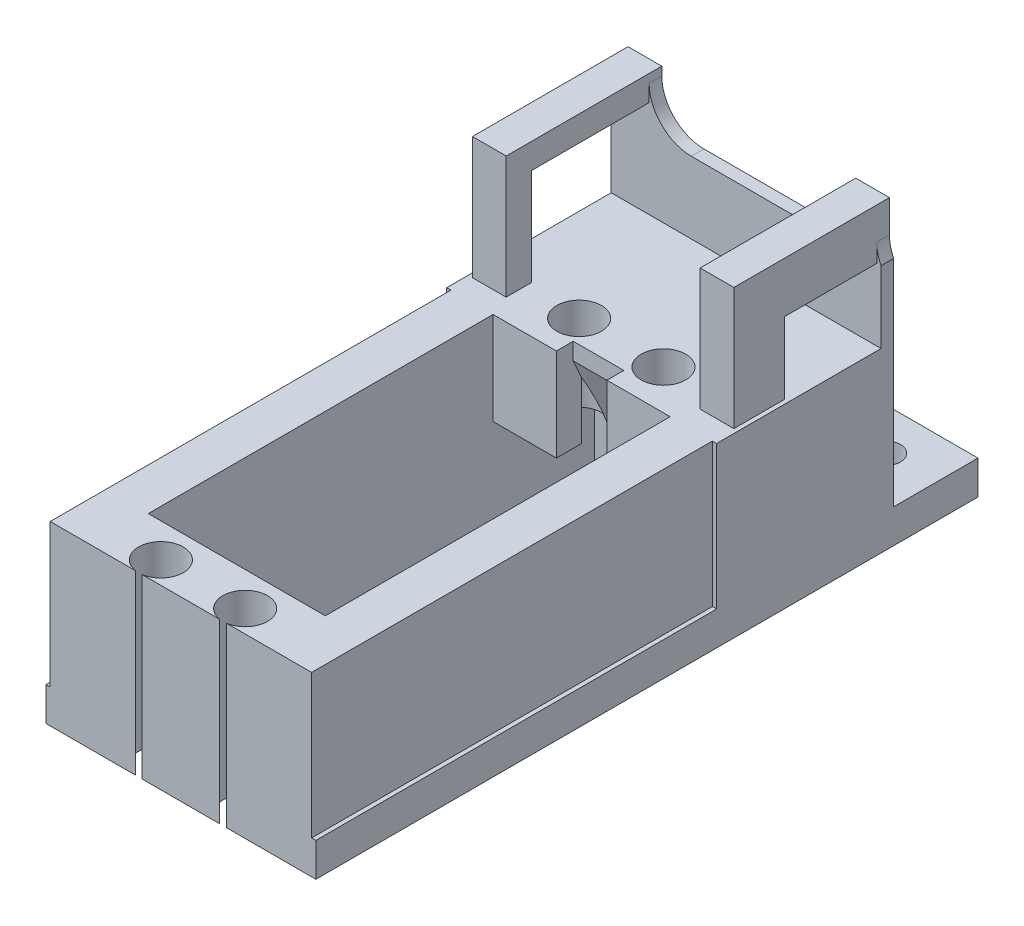
SolidWorks part; units mm, degrees
material "PLA"
ref_plane "Front Plane" through (0, 0, 0) normal (0, 0, 1) x (1, 0, 0)
ref_plane "Top Plane" through (0, 0, 0) normal (0, 1, 0) x (1, 0, 0)
ref_plane "Right Plane" through (0, 0, 0) normal (1, 0, 0) x (0, 0, -1)
sketch "Sketch1" plane through (0, 0, 0) normal (0, 1, 0) x (1, 0, 0)
  line L0 (-16, 0) -> (16, 0)
  line L1 (16, 0) -> (16, 78.52)
  line L2 (16, 78.52) -> (-16, 78.52)
  line L3 (-16, 78.52) -> (-16, 0)
  line L7 (-10, 73.52) -> (10, 73.52) construction
  point P7 (-10, 73.52)
  point P8 (10, 73.52)
  point P11 (0, 0)
  point P12 (0, 73.52)
  dimension "D1" = 20
  dimension "D2" = 78.52
  dimension "D3" = 32
  dimension "D5" = 5
extrude "Boss-Extrude1" add sketch "Sketch1" along normal blind 4 contours L2 L3 L0 L1 | L0 region at (0, 0, -39.26)
hole_wizard "M3 Clearance Hole1" positions "Sketch3" profile "Sketch4" hole size "M3" standard "ISO"
sketch "Sketch3" plane through (0, 4, 0) normal (0, 1, 0) x (1, 0, 0)
  point P0 (-10, 73.52)
  point P3 (10, 73.52)
sketch "Sketch4" plane through (-10, 4, -73.52) normal (1, 0, 0) x (0, 0, 1)
  line L0 (0, 0) -> (0, 11.0815)
  line L1 (0, 11.0815) -> (1.8, 10)
  line L2 (1.8, 10) -> (1.8, 0)
  line L5 (1.8, 0) -> (0, 0)
  line L10 (0, 11.0815) -> (-1.8, 10) construction
  line L11 (0, -6.35) -> (0, 107.95) construction
  dimension "Hole Dia." = 3.6
  dimension "Hole Depth" = 10
  dimension "Drill Angle" = 118
sketch "Sketch5" plane through (0, 4, 0) normal (0, 1, 0) x (1, 0, 0)
  line L0 (-16, 68.52) -> (16, 68.52)
  line L1 (-16, 78.52) -> (-16, 0) construction
  line L2 (16, 0) -> (16, 78.52) construction
  line L3 (16, 68.52) -> (16, 47.52)
  line L4 (16, 47.52) -> (-16, 47.52)
  line L5 (-16, 47.52) -> (-16, 68.52)
  line L6 (-15.5, 47.52) -> (-15.5, 0)
  line L7 (-16, 0) -> (16, 0) construction
  line L8 (-15.5, 0) -> (15.5, 0)
  line L9 (10.5, 47.52) -> (10.5, 6.6222)
  line L10 (10.5, 6.6222) -> (-10.5, 6.6222)
  line L11 (-10.5, 6.6222) -> (-10.5, 47.52)
  line L12 (16, 78.52) -> (-16, 78.52) construction
  line L13 (15.5, 0) -> (15.5, 47.52)
  point P18 (0, 6.6222)
  line M6 (-16, 78.52) -> (-16, 0)
  line M7 (-16, 0) -> (16, 0)
  line M8 (16, 0) -> (16, 78.52)
  dimension "D1" = 10
  dimension "D2" = 40.8978
  dimension "D3" = 21
  dimension "D4" = 6.6222
  dimension "D5" = 5
  dimension "D6" = 5
extrude "Boss-Extrude2" add sketch "Sketch5" along normal blind 17 contours L4 L0 M8 M6 region at (0, 4, -58.02)
extrude "Boss-Extrude3" add sketch "Sketch5<4>" along normal blind 17 contours L13 L4 L9 L10 L11 L6 M7 region at (-13, 4, -46.9526)
sketch "Sketch5<4>" plane through (0, 4, 0) normal (0, 1, 0) x (1, 0, 0) same geometry as "Sketch5"
sketch "Sketch6" plane through (0, 21, 0) normal (0, 1, 0) x (1, 0, 0)
  line L0 (-16, 68.52) -> (-16, 67.02)
  line L1 (-16, 68.52) -> (-16, 47.52) construction
  line L4 (-16, 68.52) -> (16, 68.52) construction
  line L7 (-16, 68.52) -> (16, 68.52) construction
  line L8 (-16, 67.02) -> (16, 67.02)
  line L9 (16, 47.52) -> (16, 68.52) construction
  line L10 (16, 67.02) -> (16, 68.52)
  line L11 (16, 68.52) -> (-16, 68.52)
  line L12 (11.5, 56.07) -> (15.5, 56.07)
  line L14 (15.5, 0) -> (15.5, 47.52) construction
  line L15 (15.5, 56.07) -> (15.5, 50.07)
  line L16 (15.5, 0) -> (15.5, 47.52) construction
  line L17 (15.5, 50.07) -> (11.5, 50.07)
  line L18 (11.5, 50.07) -> (11.5, 56.07)
  line L19 (-11.5, 56.07) -> (-11.5, 50.07)
  line L21 (-11.5, 50.07) -> (-15.5, 50.07)
  line L22 (-15.5, 47.52) -> (-15.5, 0) construction
  line L23 (-15.5, 50.07) -> (-15.5, 56.07)
  line L24 (-15.5, 56.07) -> (-11.5, 56.07)
  line L25 (-10.5, 6.6222) -> (-10.5, 47.52) construction
  point P9 (-15.5, 53.07)
  point P19 (15.5, 53.07)
  point P37 (-13.5, 50.07)
  dimension "D1" = 1.5
  dimension "D2" = 6
  dimension "D3" = 12.45
  dimension "D4" = 4
  dimension "D5" = 4
extrude "Boss-Extrude4" add sketch "Sketch6" along normal blind 8.5
sketch "Sketch10" plane through (0, 0, -47.52) normal (0, 0, 1) x (1, 0, 0)
  line L0 (-15.75, 21) -> (-15.75, 14) construction
  line L1 (-16, 21) -> (16, 21) construction
  line L2 (-15.75, 14) -> (15.75, 14) construction
  line L3 (15.75, 14) -> (15.75, 21) construction
  line L4 (16, 21) -> (15.5, 21) construction
  line L5 (15.5, 21) -> (15.5, 4) construction
  line L6 (16, 21) -> (16, 4) construction
  line L7 (-16, 21) -> (-16, 4) construction
  line L8 (-15.5, 21) -> (-15.5, 4) construction
  line L9 (-15.5, 4) -> (-16, 4) construction
  point P0 (-15.75, 14)
  point P1 (15.75, 14)
  dimension "D1" = 10
sketch "Sketch14" plane through (0, 29.5, 0) normal (0, 1, 0) x (1, 0, 0)
  line L0 (-16, 68.52) -> (16, 68.52) construction
  line L1 (-11.5, 50.07) -> (-15.5, 50.07)
  line L2 (-11.5, 50.07) -> (-11.5, 68.52)
  line L3 (-11.5, 68.52) -> (-15.5, 68.52)
  line L4 (-15.5, 50.07) -> (-15.5, 68.52)
  line L5 (-15.5, 56.07) -> (-15.5, 50.07) construction
  line L6 (16, 68.52) -> (-16, 68.52) construction
  line L7 (11.5, 50.07) -> (15.5, 50.07)
  line L8 (11.5, 50.07) -> (11.5, 68.52)
  line L9 (11.5, 68.52) -> (15.5, 68.52)
  line L10 (15.5, 50.07) -> (15.5, 68.52)
  line L11 (15.5, 50.07) -> (15.5, 56.07) construction
extrude "Boss-Extrude5" add sketch "Sketch14" along normal blind 6
fillet "Fillet1" radius 5 4 edges at (-15.5, 29.5, -67.77) (11.5, 29.5, -67.77) (15.5, 29.5, -67.77) (-11.5, 29.5, -67.77)
chamfer "Chamfer1" distance 3 angle 45 2 edges at (11.5, 29.5, -61.545) (-11.5, 29.5, -61.545)
chamfer "Chamfer2" distance 3 angle 45 2 edges at (11.5, 26.75, -56.07) (-11.5, 26.75, -56.07)
sketch "Sketch15" plane through (0, 4, 0) normal (0, 1, 0) x (1, 0, 0)
  line L4 (-10.5, 6.6222) -> (10.5, 6.6222)
  line L5 (10.5, 6.6222) -> (10.5, 47.52)
  line L6 (10.5, 47.52) -> (-10.5, 47.52)
  line L7 (-10.5, 47.52) -> (-10.5, 6.6222)
  line L8 (-10.5, 6.6222) -> (10.5, 6.6222)
  line L9 (10.5, 6.6222) -> (10.5, 47.52)
  line L10 (10.5, 47.52) -> (-10.5, 47.52)
  line L11 (-10.5, 47.52) -> (-10.5, 6.6222)
  dimension "D1" = 0
extrude "Cut-Extrude1" cut sketch "Sketch15" against normal through all both and the other way through all
sketch "Sketch16" plane through (0, 21, 0) normal (0, 1, 0) x (1, 0, 0)
  line L0 (10.5, 47.52) -> (-10.5, 47.52) construction
  line L1 (-5, 52.22) -> (5, 52.22) construction
  line L2 (-5, 2.62) -> (5, 2.62) construction
  line L4 (-15.5, 0) -> (15.5, 0) construction
  point P0 (-5, 52.22)
  point P1 (5, 52.22)
  point P6 (0, 52.22)
  point P7 (-5, 2.62)
  point P9 (5, 2.62)
  dimension "D1" = 10
  dimension "D2" = 4.7
  dimension "D3" = 2.62
hole_wizard "Ø5.3 (5.3) Diameter Hole1" positions "Sketch17" profile "Sketch18" hole size "Ø5.3" standard "ISO" end condition through all
sketch "Sketch17" plane through (0, 21, 0) normal (0, 1, 0) x (1, 0, 0)
  point P0 (-5, 52.22)
  point P3 (5, 52.22)
  point P6 (-5, 2.62)
  point P9 (5, 2.62)
sketch "Sketch18" plane through (-5, 21, -52.22) normal (1, 0, 0) x (0, 0, 1)
  line L0 (0, 0) -> (0, 21)
  line L1 (0, 21) -> (2.65, 21)
  line L2 (2.65, 21) -> (2.65, 0)
  line L5 (2.65, 0) -> (0, 0)
  line L11 (0, -6.35) -> (0, 107.95) construction
  dimension "Thru Hole Dia." = 5.3
  dimension "Thru Hole Depth" = 21
sketch "Sketch19" plane through (0, 0, 0) normal (0, -1, 0) x (1, 0, 0)
  line L1 (-10.5, -47.52) -> (10.5, -47.52)
  line L2 (-10.5, -47.52) -> (-10.5, -59.52)
  line L3 (-10.5, -59.52) -> (10.5, -59.52)
  line L4 (10.5, -47.52) -> (10.5, -59.52)
  dimension "D1" = 12
extrude "Cut-Extrude2" cut sketch "Sketch19" against normal blind 10
sketch "Sketch20" plane through (0, 21, 0) normal (0, 1, 0) x (1, 0, 0)
  line L0 (10.5, 47.52) -> (-10.5, 47.52) construction
  line L1 (-3, 47.52) -> (3, 47.52)
  line L2 (-3, 47.52) -> (-3, 49.52)
  line L3 (-3, 49.52) -> (3, 49.52)
  line L4 (3, 47.52) -> (3, 49.52)
  point P6 (0, 47.52)
  point P7 (0, 47.52)
  dimension "D1" = 6
  dimension "D2" = 2
extrude "Cut-Extrude3" cut sketch "Sketch20" against normal through all both and the other way through all
chamfer "Chamfer3" distance 4 angle 66 1 edges at (0, 10, -49.52) first distance on face at (0, 10, -51.02)
